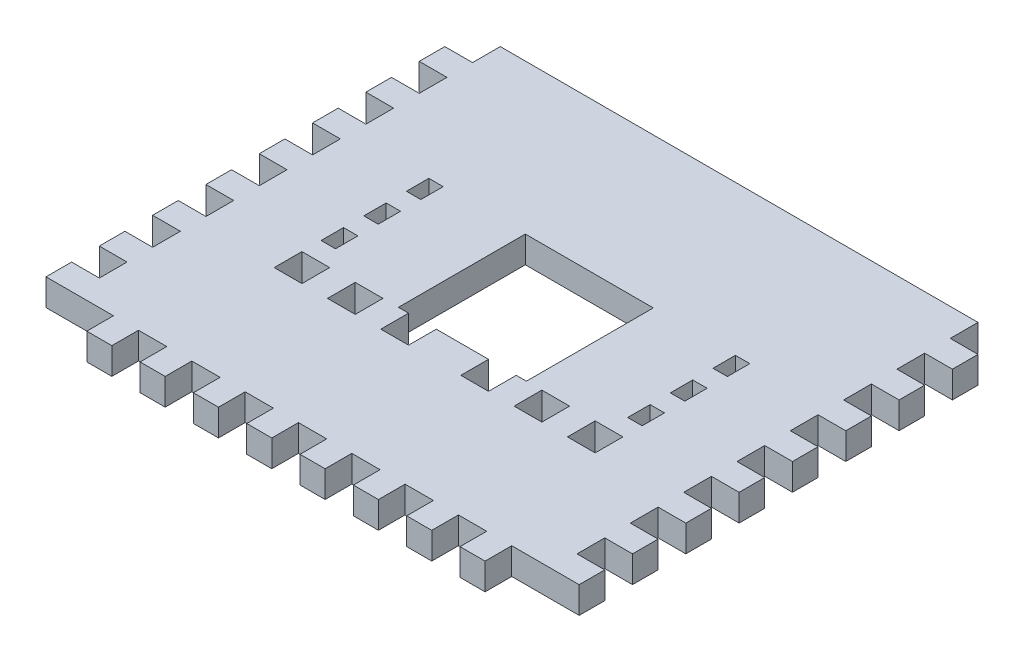
SolidWorks part; units mm, degrees
ref_plane "Front Plane" through (0, 0, 0) normal (0, 0, 1) x (1, 0, 0)
ref_plane "Top Plane" through (0, 0, 0) normal (0, 1, 0) x (1, 0, 0)
ref_plane "Right Plane" through (0, 0, 0) normal (1, 0, 0) x (0, 0, -1)
sketch "Sketch1" plane through (0, 0, 0) normal (0, 1, 0) x (1, 0, 0)
  line L1 (-63.5, -53.975) -> (63.5, -53.975)
  line L2 (-63.5, -53.975) -> (-63.5, 53.975)
  line L3 (-63.5, 53.975) -> (63.5, 53.975)
  line L4 (63.5, -53.975) -> (63.5, 53.975)
  line L5 (-63.5, -53.975) -> (63.5, 53.975) construction
  line L6 (-63.5, 53.975) -> (63.5, -53.975) construction
  point P0 (0, 0)
  dimension "D1" = 127
  dimension "D2" = 107.95
extrude "Boss-Extrude1" add sketch "Sketch1" along normal blind 6.35
sketch "Sketch2" plane through (0, 0, 0) normal (0, -1, 0) x (1, 0, 0)
  line L0 (-34.7345, 47.625) -> (-41.4655, 47.625)
  line L5 (63.5, 53.975) -> (63.5, -53.975) construction
  line L34 (0, 0) -> (0, -14.8721) construction
  line L39 (63.5, 41.529) -> (56.896, 41.529)
  line L41 (63.5, 54.229) -> (63.5, 47.625)
  line L42 (63.5, 47.625) -> (56.896, 47.625)
  line L44 (63.5, 41.529) -> (63.5, 34.925)
  line L45 (63.5, 34.925) -> (56.896, 34.925)
  line L46 (56.896, 41.529) -> (56.896, 34.925)
  line L47 (63.5, 28.829) -> (56.896, 28.829)
  line L48 (63.5, 28.829) -> (63.5, 22.225)
  line L49 (63.5, 22.225) -> (56.896, 22.225)
  line L50 (56.896, 28.829) -> (56.896, 22.225)
  line L51 (63.5, 16.129) -> (56.896, 16.129)
  line L52 (63.5, 16.129) -> (63.5, 9.525)
  line L53 (63.5, 9.525) -> (56.896, 9.525)
  line L54 (56.896, 16.129) -> (56.896, 9.525)
  line L55 (63.5, 3.429) -> (56.896, 3.429)
  line L56 (63.5, 3.429) -> (63.5, -3.175)
  line L57 (63.5, -3.175) -> (56.896, -3.175)
  line L58 (56.896, 3.429) -> (56.896, -3.175)
  line L59 (63.5, -9.271) -> (56.896, -9.271)
  line L60 (63.5, -9.271) -> (63.5, -15.875)
  line L61 (63.5, -15.875) -> (56.896, -15.875)
  line L62 (56.896, -9.271) -> (56.896, -15.875)
  line L63 (63.5, -21.971) -> (56.896, -21.971)
  line L64 (63.5, -21.971) -> (63.5, -28.575)
  line L65 (63.5, -28.575) -> (56.896, -28.575)
  line L66 (56.896, -21.971) -> (56.896, -28.575)
  line L67 (63.5, -34.671) -> (56.896, -34.671)
  line L68 (63.5, -34.671) -> (63.5, -41.275)
  line L69 (63.5, -41.275) -> (56.896, -41.275)
  line L70 (56.896, -34.671) -> (56.896, -41.275)
  line L71 (-56.896, -34.671) -> (-56.896, -41.275)
  line L72 (-63.5, -41.275) -> (-56.896, -41.275)
  line L73 (-63.5, -34.671) -> (-63.5, -41.275)
  line L74 (-63.5, -34.671) -> (-56.896, -34.671)
  line L75 (-56.896, -21.971) -> (-56.896, -28.575)
  line L76 (-63.5, -28.575) -> (-56.896, -28.575)
  line L77 (-63.5, -21.971) -> (-63.5, -28.575)
  line L78 (-63.5, -21.971) -> (-56.896, -21.971)
  line L79 (-56.896, -9.271) -> (-56.896, -15.875)
  line L80 (-63.5, -15.875) -> (-56.896, -15.875)
  line L81 (-63.5, -9.271) -> (-63.5, -15.875)
  line L82 (-63.5, -9.271) -> (-56.896, -9.271)
  line L83 (-56.896, 3.429) -> (-56.896, -3.175)
  line L84 (-63.5, -3.175) -> (-56.896, -3.175)
  line L85 (-63.5, 3.429) -> (-63.5, -3.175)
  line L86 (-63.5, 3.429) -> (-56.896, 3.429)
  line L87 (-56.896, 16.129) -> (-56.896, 9.525)
  line L88 (-63.5, 9.525) -> (-56.896, 9.525)
  line L89 (-63.5, 16.129) -> (-63.5, 9.525)
  line L90 (-63.5, 16.129) -> (-56.896, 16.129)
  line L91 (-56.896, 28.829) -> (-56.896, 22.225)
  line L92 (-63.5, 22.225) -> (-56.896, 22.225)
  line L93 (-63.5, 28.829) -> (-63.5, 22.225)
  line L94 (-63.5, 28.829) -> (-56.896, 28.829)
  line L95 (-56.896, 41.529) -> (-56.896, 34.925)
  line L96 (-63.5, 34.925) -> (-56.896, 34.925)
  line L97 (-63.5, 41.529) -> (-63.5, 34.925)
  line L99 (-63.5, 47.625) -> (-56.896, 47.625)
  line L100 (-63.5, 54.229) -> (-63.5, 47.625)
  line L102 (-63.5, 41.529) -> (-56.896, 41.529)
  line L103 (56.896, 47.625) -> (47.4345, 47.625)
  line L104 (34.7345, 47.625) -> (34.7345, 54.229)
  line L106 (34.7345, 54.229) -> (28.7655, 54.229)
  line L107 (28.7655, 54.229) -> (28.7655, 47.625)
  line L108 (28.7655, 47.625) -> (22.0345, 47.625)
  line L109 (22.0345, 47.625) -> (22.0345, 54.229)
  line L110 (22.0345, 54.229) -> (16.0655, 54.229)
  line L111 (16.0655, 54.229) -> (16.0655, 47.625)
  line L112 (16.0655, 47.625) -> (9.3345, 47.625)
  line L113 (9.3345, 47.625) -> (9.3345, 54.229)
  line L114 (9.3345, 54.229) -> (3.3655, 54.229)
  line L115 (3.3655, 54.229) -> (3.3655, 47.625)
  line L116 (3.3655, 47.625) -> (-3.3655, 47.625)
  line L117 (-3.3655, 47.625) -> (-3.3655, 54.229)
  line L118 (-3.3655, 54.229) -> (-9.3345, 54.229)
  line L119 (-9.3345, 54.229) -> (-9.3345, 47.625)
  line L120 (-9.3345, 47.625) -> (-16.0655, 47.625)
  line L121 (-16.0655, 47.625) -> (-16.0655, 54.229)
  line L122 (-16.0655, 54.229) -> (-22.0345, 54.229)
  line L123 (-22.0345, 54.229) -> (-22.0345, 47.625)
  line L124 (-22.0345, 47.625) -> (-28.7655, 47.625)
  line L125 (-28.7655, 47.625) -> (-28.7655, 54.229)
  line L126 (-28.7655, 54.229) -> (-34.7345, 54.229)
  line L127 (-34.7345, 54.229) -> (-34.7345, 47.625)
  line L137 (-63.5, 54.229) -> (-63.5, 63.0316)
  line L138 (63.5, -53.975) -> (-63.5, -53.975) construction
  line L139 (-63.5, 63.0316) -> (63.5, 63.0316)
  line L140 (63.5, 63.0316) -> (63.5, 54.229)
  line L141 (63.5, -47.371) -> (63.5, -53.975)
  line L142 (63.5, -53.975) -> (56.896, -53.975)
  line L143 (56.896, -53.975) -> (56.896, -47.371)
  line L144 (56.896, -47.371) -> (63.5, -47.371)
  line L145 (-56.896, -47.371) -> (-63.5, -47.371)
  line L146 (-56.896, -53.975) -> (-56.896, -47.371)
  line L147 (-63.5, -53.975) -> (-56.896, -53.975)
  line L148 (-63.5, -47.371) -> (-63.5, -53.975)
  line L149 (-63.5, -53.975) -> (-63.5, 53.975) construction
  line L150 (63.5, 53.975) -> (63.5, -53.975) construction
  line L151 (41.4655, 47.625) -> (41.4655, 54.229)
  line L152 (41.4655, 54.229) -> (47.4345, 54.229)
  line L153 (47.4345, 54.229) -> (47.4345, 47.625)
  line L154 (-41.4655, 47.625) -> (-41.4655, 54.229)
  line L155 (-41.4655, 54.229) -> (-47.4345, 54.229)
  line L156 (-47.4345, 54.229) -> (-47.4345, 47.625)
  line L157 (-47.4345, 47.625) -> (-56.896, 47.625)
  line L158 (41.4655, 47.625) -> (34.7345, 47.625)
  point P3 (0, 47.625)
  dimension "D2" = 6.604
  dimension "D3" = 5.969
  dimension "D6" = 6.731
  dimension "D8" = 6.604
  dimension "D9" = 9
extrude "Cut-Extrude1" cut sketch "Sketch2" against normal through all
ref_plane "Plane1" through (0, 0, -3.175) normal (0, 0, -1) x (-1, 0, 0)
ref_plane "Plane2" through (0, 0, 0) normal (-1, 0, 0) x (0, 0, 1)
ref_axis "Axis1" through (0, 3.3337, -3.175) along (0, -1, 0)
sketch "Sketch3" plane through (0, 0, 0) normal (0, 1, 0) x (1, 0, 0)
  line L0 (-38.227, 8.128) -> (-34.798, 8.128)
  line L1 (15.24, 18.288) -> (-15.24, 18.288)
  line L2 (15.24, 18.288) -> (15.24, -11.938)
  line L3 (15.24, -11.938) -> (12.827, -11.938)
  line L4 (-15.24, 18.288) -> (-15.24, -11.938)
  line L5 (0, -12.065) -> (0, 18.288) construction
  line L6 (15.24, 3.175) -> (-15.24, 3.175) construction
  line L7 (-38.227, 18.288) -> (-34.798, 18.288)
  line L8 (-38.227, 18.288) -> (-38.227, 12.954)
  line L9 (-38.227, 12.954) -> (-34.798, 12.954)
  line L10 (-34.798, 18.288) -> (-34.798, 12.954)
  line L11 (-38.227, 18.288) -> (-34.798, 12.954) construction
  line L12 (-38.227, 12.954) -> (-34.798, 18.288) construction
  line L13 (-38.227, 8.128) -> (-38.227, 2.794)
  line L14 (-38.227, 2.794) -> (-34.798, 2.794)
  line L15 (-34.798, 8.128) -> (-34.798, 2.794)
  line L16 (-38.227, 8.128) -> (-34.798, 2.794) construction
  line L17 (-38.227, 2.794) -> (-34.798, 8.128) construction
  line L18 (-38.227, -2.032) -> (-34.798, -2.032)
  line L19 (-38.227, -2.032) -> (-38.227, -7.366)
  line L20 (-38.227, -7.366) -> (-34.798, -7.366)
  line L21 (-34.798, -2.032) -> (-34.798, -7.366)
  line L22 (-38.227, -2.032) -> (-34.798, -7.366) construction
  line L23 (-38.227, -7.366) -> (-34.798, -2.032) construction
  line L24 (-25.527, -11.938) -> (-18.923, -11.938)
  line L25 (-38.227, -11.938) -> (-31.623, -11.938)
  line L26 (-38.227, -11.938) -> (-38.227, -18.542)
  line L27 (-38.227, -18.542) -> (-31.623, -18.542)
  line L28 (-31.623, -11.938) -> (-31.623, -18.542)
  line L29 (-38.227, -11.938) -> (-31.623, -18.542) construction
  line L30 (-38.227, -18.542) -> (-31.623, -11.938) construction
  line L31 (-25.527, -11.938) -> (-25.527, -18.542)
  line L32 (-25.527, -18.542) -> (-18.923, -18.542)
  line L33 (-18.923, -11.938) -> (-18.923, -18.542)
  line L34 (-25.527, -11.938) -> (-18.923, -18.542) construction
  line L35 (-25.527, -18.542) -> (-18.923, -11.938) construction
  line L37 (-12.827, -11.938) -> (-12.827, -18.542)
  line L38 (-12.827, -18.542) -> (-6.223, -18.542)
  line L39 (-6.223, -11.938) -> (-6.223, -18.542)
  line L40 (-12.827, -11.938) -> (-6.223, -18.542) construction
  line L41 (-12.827, -18.542) -> (-6.223, -11.938) construction
  line L42 (12.827, -18.542) -> (6.223, -11.938) construction
  line L43 (12.827, -11.938) -> (6.223, -18.542) construction
  line L44 (25.527, -18.542) -> (18.923, -11.938) construction
  line L45 (25.527, -11.938) -> (18.923, -18.542) construction
  line L46 (38.227, -18.542) -> (31.623, -11.938) construction
  line L47 (38.227, -11.938) -> (31.623, -18.542) construction
  line L48 (38.227, -7.366) -> (34.798, -2.032) construction
  line L49 (38.227, -2.032) -> (34.798, -7.366) construction
  line L50 (38.227, 2.794) -> (34.798, 8.128) construction
  line L51 (38.227, 8.128) -> (34.798, 2.794) construction
  line L52 (38.227, 12.954) -> (34.798, 18.288) construction
  line L53 (38.227, 18.288) -> (34.798, 12.954) construction
  line L54 (6.223, -11.938) -> (6.223, -18.542)
  line L55 (12.827, -18.542) -> (6.223, -18.542)
  line L56 (12.827, -11.938) -> (12.827, -18.542)
  line L58 (18.923, -11.938) -> (18.923, -18.542)
  line L59 (25.527, -18.542) -> (18.923, -18.542)
  line L60 (25.527, -11.938) -> (25.527, -18.542)
  line L61 (31.623, -11.938) -> (31.623, -18.542)
  line L62 (38.227, -18.542) -> (31.623, -18.542)
  line L63 (38.227, -11.938) -> (38.227, -18.542)
  line L64 (38.227, -11.938) -> (31.623, -11.938)
  line L65 (25.527, -11.938) -> (18.923, -11.938)
  line L66 (34.798, -2.032) -> (34.798, -7.366)
  line L67 (38.227, -7.366) -> (34.798, -7.366)
  line L68 (38.227, -2.032) -> (38.227, -7.366)
  line L69 (38.227, -2.032) -> (34.798, -2.032)
  line L70 (34.798, 8.128) -> (34.798, 2.794)
  line L71 (38.227, 2.794) -> (34.798, 2.794)
  line L72 (38.227, 8.128) -> (38.227, 2.794)
  line L73 (34.798, 18.288) -> (34.798, 12.954)
  line L74 (38.227, 12.954) -> (34.798, 12.954)
  line L75 (38.227, 18.288) -> (38.227, 12.954)
  line L76 (38.227, 18.288) -> (34.798, 18.288)
  line L77 (38.227, 8.128) -> (34.798, 8.128)
  line L78 (-12.827, -11.938) -> (-15.24, -11.938)
  line L79 (-12.827, -11.938) -> (-6.223, -11.938) [skipped]
  line L80 (6.223, -11.938) -> (-6.223, -11.938)
  point P0 (0, 3.175)
  point P9 (-36.5125, 15.621)
  point P16 (-36.5125, 5.461)
  point P21 (-36.5125, -4.699)
  point P24 (-34.925, -15.24)
  point P30 (-22.225, -15.24)
  point P34 (-9.525, -15.24)
  point P59 (9.525, -15.24)
  point P60 (22.225, -15.24)
  point P61 (34.925, -15.24)
  point P62 (36.5125, -4.699)
  point P63 (36.5125, 5.461)
  point P64 (36.5125, 15.621)
  dimension "D1" = 3.429
  dimension "D2" = 30.48
  dimension "D3" = 5.334
  dimension "D4" = 36.5125
  dimension "D6" = 6.604
  dimension "D7" = 6.604
  dimension "D9" = 10.16
  dimension "D10" = 12.7
  dimension "D11" = 18.415
  dimension "D5" = 3
  dimension "D8" = 3
extrude "Cut-Extrude4" cut sketch "Sketch3" along normal through all
